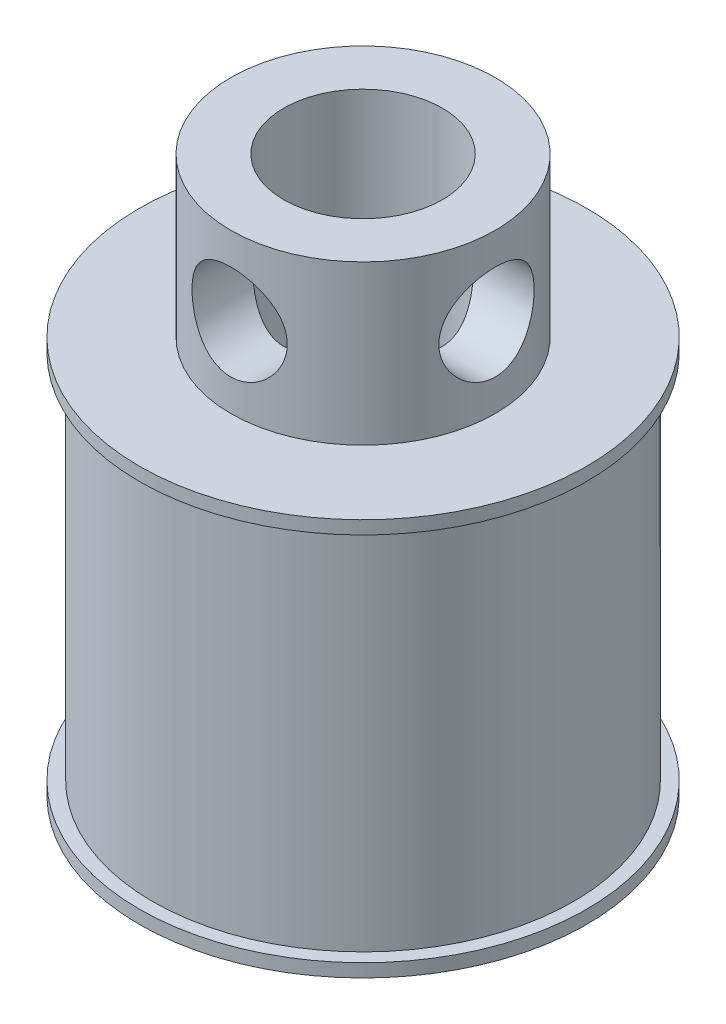
SolidWorks part; units mm, degrees
ref_plane "Alzado" through (0, 0, 0) normal (1, 0, 0) x (0, 1, 0)
ref_plane "Planta" through (0, 0, 0) normal (0, 0, 1) x (0, 1, 0)
ref_plane "Vista lateral" through (0, 0, 0) normal (0, 1, 0) x (-1, 0, 0)
sketch "Croquis1" plane through (0, 0, 0) normal (0, 1, 0) x (-1, 0, 0)
  circle A0 centre (0, 0) radius 7.95
  dimension "D1" = 15.9
extrude "Saliente-Extruir1" add sketch "Croquis1" along normal mid plane 15
sketch "Croquis2" plane through (0, 7.5, 0) normal (0, 1, 0) x (-1, 0, 0)
  circle A3 centre (0, 0) radius 8.45
  dimension "D1" = 16.9
extrude "Saliente-Extruir2" add sketch "Croquis2" against normal blind 0.5
extrude "Saliente-Extruir3" add sketch "Croquis2<2>" along normal blind 0.5 from surface starting at face at (0, -7.5, 7.95)
sketch "Croquis2<2>" plane through (0, 7.5, 0) normal (0, 1, 0) x (-1, 0, 0) same geometry as "Croquis2"
sketch "Croquis3" plane through (0, -7.5, 0) normal (0, 1, 0) x (-1, 0, 0)
  circle A0 centre (0, 0) radius 5
  dimension "D1" = 10
extrude "Saliente-Extruir4" add sketch "Croquis3" along normal blind 21
sketch "Croquis4" plane through (0, -7, 0) normal (0, 1, 0) x (-1, 0, 0)
  circle A0 centre (0, 0) radius 3
  dimension "D1" = 6
extrude "Cortar-Extruir1" cut sketch "Croquis4" against normal through all both and the other way through all
sketch "Croquis5" plane through (0, 0, 0) normal (0, 0, 1) x (0, 1, 0)
  line L4 (10.5, 5) -> (10.5, -5) construction
  line L5 (13.5, 5) -> (7.5, 5) construction
  line L9 (7.5, -5) -> (7.5, 5) construction
  line L10 (7.5, -5) -> (7.5, 5) construction
  point P10 (10.5, 0)
sketch "Croquis6" plane through (0, 0, 0) normal (1, 0, 0) x (0, 1, 0)
  point P0 (10.5, 0)
hole_wizard "Taladro de margen para M31" positions "Croquis6" profile "Croquis7" hole size "M3" standard "Ansi Metric" end condition up to next
sketch "Croquis7" plane through (0, 10.5, 0) normal (0, 1, 0) x (0, 0, 1)
  line L0 (0, 0) -> (0, 5)
  line L1 (0, 5) -> (1.8, 5)
  line L2 (1.8, 5) -> (1.8, 0)
  line L5 (1.8, 0) -> (0, 0)
  line L11 (0, -6.35) -> (0, 107.95) construction
  dimension "Diámetro de taladro hasta el siguiente" = 3.6
  dimension "Profundidad de taladro hasta el siguiente" = 5
hole_wizard "Taladro de margen para M32" positions "Croquis5" profile "Croquis9" hole size "M3" standard "Ansi Metric" end condition up to next
sketch "Croquis9" plane through (0, 10.5, 0) normal (1, 0, 0) x (0, 1, 0)
  line L0 (0, 0) -> (0, 5)
  line L1 (0, 5) -> (1.8, 5)
  line L2 (1.8, 5) -> (1.8, 0)
  line L5 (1.8, 0) -> (0, 0)
  line L11 (0, -6.35) -> (0, 107.95) construction
  dimension "Diámetro de taladro hasta el siguiente" = 3.6
  dimension "Profundidad de taladro hasta el siguiente" = 5
equation "\"Dp\"= 15.9"
equation "\"D1@Croquis1\"=\"Dp\""
equation "\"Dm\"= 10"
equation "\"De\"= \"Dp\" + 1"
equation "\"F\"= 15"
equation "\"L\"= 21"
equation "\"D1@Croquis2\"=\"De\""
equation "\"D1@Saliente-Extruir1\"=\"F\""
equation "\"D1@Saliente-Extruir4\"=\"L\""
equation "\"agujero\"= 6"
equation "\"D1@Croquis4\"=\"agujero\""
